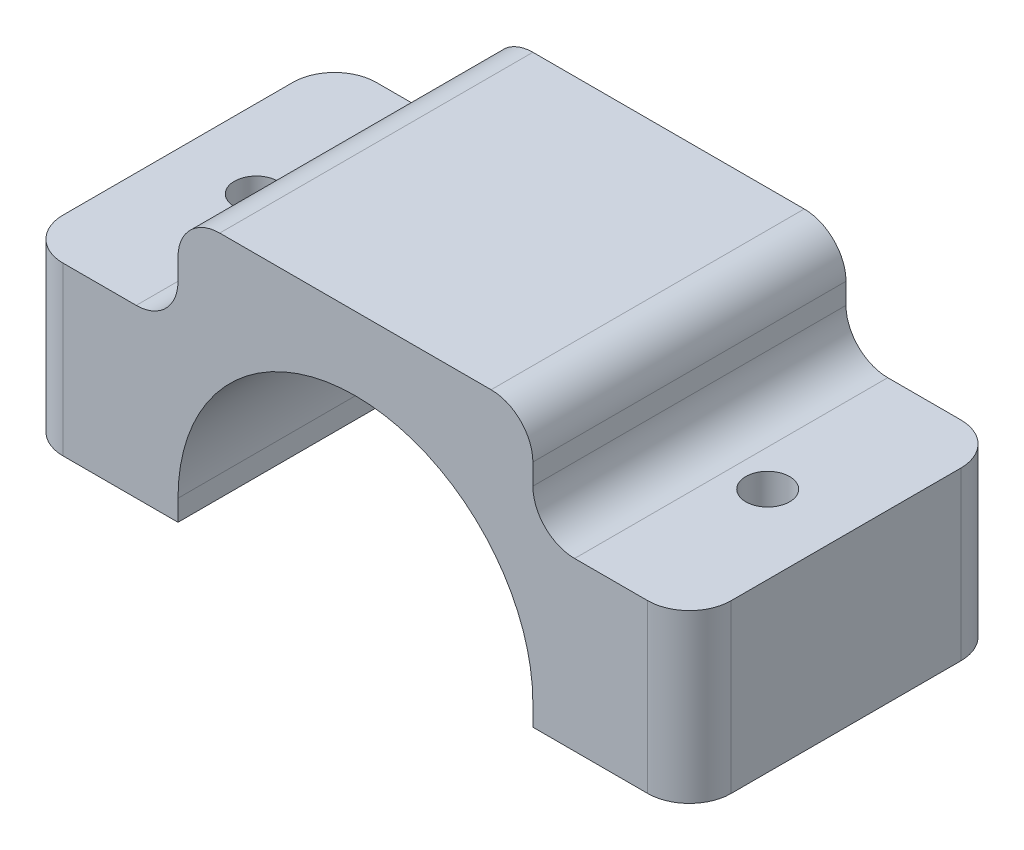
SolidWorks part; units mm, degrees
ref_plane "Front Plane" through (0, 0, 0) normal (0, 0, 1) x (1, 0, 0)
ref_plane "Top Plane" through (0, 0, 0) normal (0, 1, 0) x (1, 0, 0)
ref_plane "Right Plane" through (0, 0, 0) normal (1, 0, 0) x (0, 0, -1)
sketch "Sketch1" plane through (0, 0, 0) normal (0, 0, 1) x (1, 0, 0)
  line L0 (-16, 0) -> (-8.5, 0)
  line L1 (16, -12) -> (-16, -12)
  line L2 (16, -12) -> (16, 12)
  line L3 (16, 12) -> (-16, 12)
  line L4 (-16, -12) -> (-16, 12)
  line L5 (0, 12) -> (0, -12) construction
  line L6 (16, 0) -> (-16, 0) construction
  line L7 (8.5, 0) -> (16, 0)
  circle A0 centre (0, 0) radius 8.5
  point P0 (0, 0)
  dimension "D3" = 17
  dimension "D1" = 32
  dimension "D2" = 24
extrude "Boss-Extrude1" add sketch "Sketch1" along normal blind 15 contours A0 L7 L2 L3 L4 L0 region at (-15.6582, 6, 0)
sketch "Sketch2" plane through (0, 0, 0) normal (0, -1, 0) x (1, 0, 0)
  line L0 (-16, 15) -> (16, 15) construction
  line L1 (0, 15) -> (0, 0) construction
  line L2 (0, 0) -> (-16, 0) construction
  line L3 (-12.25, 0) -> (-12.25, 15) construction
  line L4 (-16, 0) -> (-8.5, 0)
  line L5 (-8.5, 0) -> (-8.5, 15)
  line L6 (-8.5, 15) -> (-16, 15)
  line L7 (-16, 15) -> (-16, 0)
  line L8 (-16, 0) -> (-8.5, 0)
  line L9 (-8.5, 0) -> (-8.5, 15)
  line L10 (-8.5, 15) -> (-16, 15)
  line L11 (-16, 15) -> (-16, 0)
  line L12 (8.5, 0) -> (16, 0)
  line L13 (16, 0) -> (16, 15)
  line L14 (16, 15) -> (8.5, 15)
  line L15 (8.5, 15) -> (8.5, 0)
  line L16 (8.5, 0) -> (16, 0)
  line L17 (16, 0) -> (16, 15)
  line L18 (16, 15) -> (8.5, 15)
  line L19 (8.5, 15) -> (8.5, 0)
  circle A0 centre (-12.25, 7.5) radius 1.05
  circle A1 centre (12.25, 7.5) radius 1.05
  dimension "D4" = 2.1
  dimension "D3" = 3.75
  dimension "D1" = 0
  dimension "D2" = 0
extrude "Cut-Extrude1" cut sketch "Sketch2" against normal through all both and the other way through all contours A1 | A0
fillet "Fillet1" radius 2 4 edges at (-16, 6, 0) (-16, 6, 15) (16, 6, 15) (16, 6, 0)
extrude "Cut-Extrude2" cut sketch "Sketch2<3>" along normal blind 5 from surface starting at face at (-11.2, 12, 7.5)
sketch "Sketch2<3>" plane through (0, 0, 0) normal (0, -1, 0) x (1, 0, 0) same geometry as "Sketch2"
fillet "Fillet2" radius 2 4 edges at (8.5, 12, 7.5) (-8.5, 12, 7.5) (-8.5, 7, 7.5) (8.5, 7, 7.5)
sketch "Sketch3" plane through (0, 0, 0) normal (0, -1, 0) x (1, 0, 0)
  line L4 (-16, 13) -> (-16, 2)
  line L5 (-14, 0) -> (-8.5, 0)
  line L6 (-8.5, 0) -> (-8.5, 15)
  line L7 (-8.5, 15) -> (-14, 15)
  line L8 (-16, 13) -> (-16, 2)
  line L9 (-14, 0) -> (-8.5, 0)
  line L10 (-8.5, 0) -> (-8.5, 15)
  line L11 (-8.5, 15) -> (-14, 15)
  line L12 (16, 2) -> (16, 13)
  line L13 (14, 15) -> (8.5, 15)
  line L14 (8.5, 15) -> (8.5, 0)
  line L15 (8.5, 0) -> (14, 0)
  line L16 (16, 2) -> (16, 13)
  line L17 (14, 15) -> (8.5, 15)
  line L18 (8.5, 15) -> (8.5, 0)
  line L19 (8.5, 0) -> (14, 0)
  circle A0 centre (-12.25, 7.5) radius 1.05 construction
  circle A1 centre (-12.25, 7.5) radius 1.05
  arc A2 (-16, 2) -> (-14, 0) centre (-14, 2) ccw
  arc A3 (-14, 15) -> (-16, 13) centre (-14, 13) ccw
  arc A4 (-16, 2) -> (-14, 0) centre (-14, 2) ccw
  arc A5 (-14, 15) -> (-16, 13) centre (-14, 13) ccw
  arc A6 (16, 13) -> (14, 15) centre (14, 13) ccw
  arc A7 (14, 0) -> (16, 2) centre (14, 2) ccw
  arc A8 (16, 13) -> (14, 15) centre (14, 13) ccw
  arc A9 (14, 0) -> (16, 2) centre (14, 2) ccw
  circle A10 centre (12.25, 7.5) radius 1.05 construction
  circle A11 centre (12.25, 7.5) radius 1.05
  dimension "D1" = 0
  dimension "D2" = 0
extrude "Boss-Extrude2" add sketch "Sketch3" along normal blind 1
